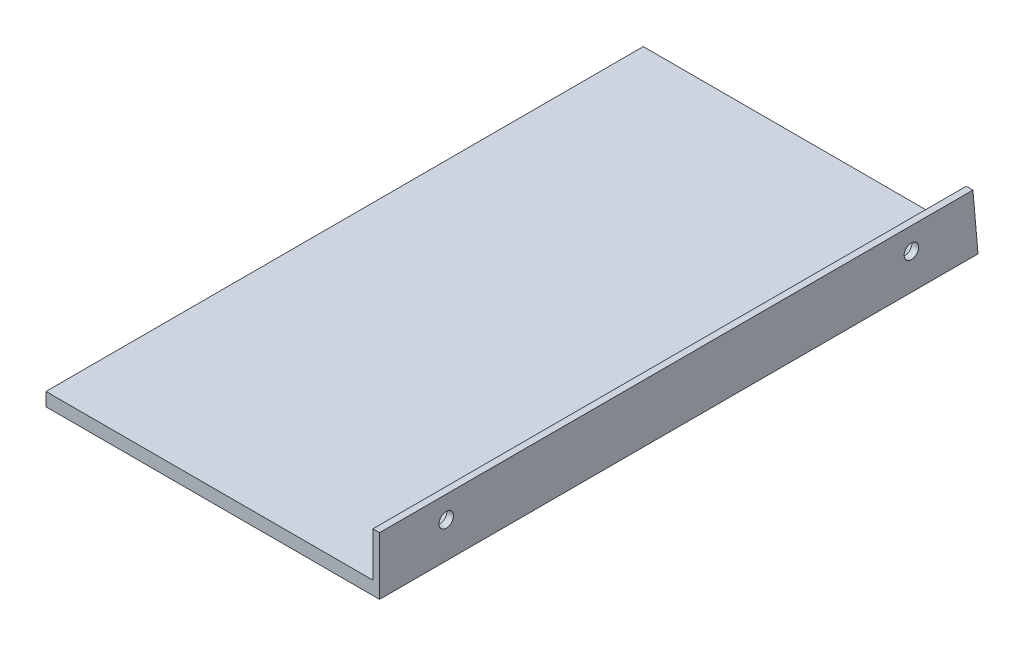
SolidWorks part; units mm, degrees
ref_plane "Front Plane" through (0, 0, 0) normal (0, 0, 1) x (1, 0, 0)
ref_plane "Top Plane" through (0, 0, 0) normal (0, 1, 0) x (1, 0, 0)
ref_plane "Right Plane" through (0, 0, 0) normal (1, 0, 0) x (0, 0, -1)
sketch "Sketch1" plane through (0, 0, 0) normal (1, 0, 0) x (0, 0, -1)
  line L1 (0, 0) -> (134.58, 0)
  line L2 (0, 0) -> (0, 3)
  line L3 (0, 3) -> (134.58, 3)
  line L4 (134.58, 0) -> (134.58, 3)
  dimension "D1" = 134.58
  dimension "D2" = 3
extrude "Boss-Extrude1" add sketch "Sketch1" along normal blind 75
sketch "Sketch2" plane through (0, 0, 0) normal (0, -1, 0) x (1, 0, 0)
  line L0 (0, 0) -> (0, -134.58) construction
  line L1 (0, -12.1) -> (3, -12.1)
  line L2 (0, -12.1) -> (0, -47.1)
  line L3 (0, -47.1) -> (3, -47.1)
  line L4 (3, -12.1) -> (3, -47.1)
  line L5 (75, 0) -> (0, 0) construction
  dimension "D1" = 12.1
  dimension "D2" = 3
  dimension "D3" = 35
extrude "Boss-Extrude2" add sketch "Sketch2" along normal blind 9
sketch "Sketch3" plane through (0, 0, 0) normal (-1, 0, 0) x (0, 0, 1)
  line L0 (-12.1, -9) -> (-47.1, -9) construction
  line L1 (-47.1, -9) -> (-47.1, 0) construction
  line L2 (-12.1, -9) -> (-12.1, 0) construction
  circle A0 centre (-23.7667, -4.5) radius 1.575
  circle A1 centre (-35.4333, -4.5) radius 1.575
  dimension "D1" = 3.15
  dimension "D2" = 3.15
  dimension "D3" = 4.5
  dimension "D4" = 4.5
  dimension "D5" = 11.6667
  dimension "D6" = 11.6667
extrude "Cut-Extrude1" cut sketch "Sketch3" against normal through all
sketch "Sketch4" plane through (0, 3, 0) normal (0, 1, 0) x (1, 0, 0)
  line L0 (75, 134.58) -> (0, 134.58) construction
  line L1 (75, 0) -> (73.5, 0)
  line L2 (75, 0) -> (75, 134.58)
  line L3 (75, 134.58) -> (73.5, 134.58)
  line L4 (73.5, 0) -> (73.5, 134.58)
  dimension "D1" = 1.5
extrude "Boss-Extrude3" add sketch "Sketch4" along normal blind 10
sketch "Sketch6" plane through (75, 0, 0) normal (1, 0, 0) x (0, 0, -1)
  line L0 (0, 13) -> (134.58, 13) construction
  line L2 (0, 13) -> (0, 0) construction
  line L3 (134.58, 0) -> (134.58, 13) construction
  line L4 (134.58, 13) -> (133.42, 13)
  line L5 (134.58, 13) -> (134.58, 0)
  line L6 (134.58, 0) -> (134.56, 0)
  line L7 (0, 0) -> (134.58, 0) construction
  line L8 (134.56, 0) -> (133.42, 13)
  circle A0 centre (15, 8) radius 1.625
  circle A1 centre (119.58, 8) radius 1.625
  dimension "D1" = 3.25
  dimension "D2" = 3.25
  dimension "D3" = 5
  dimension "D4" = 5
  dimension "D5" = 15
  dimension "D6" = 15
  dimension "D7" = 1.16
  dimension "D8" = 0.02
extrude "Cut-Extrude2" cut sketch "Sketch6" against normal through all
